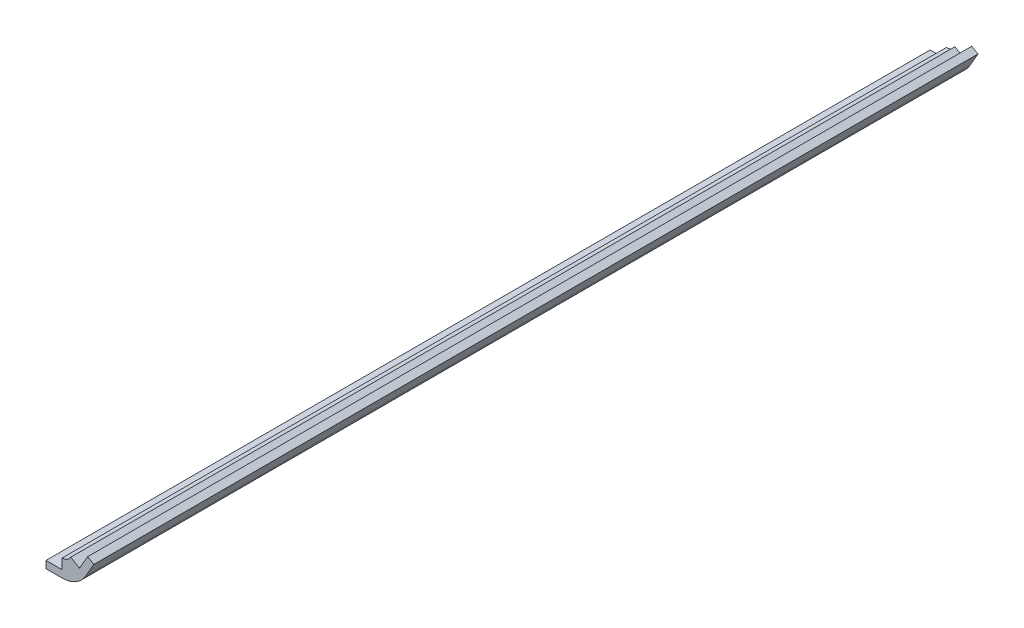
SolidWorks part; units mm, degrees
ref_plane "Front Plane" through (0, 0, 0) normal (0, 0, 1) x (1, 0, 0)
ref_plane "Top Plane" through (0, 0, 0) normal (0, 1, 0) x (1, 0, 0)
ref_plane "Right Plane" through (0, 0, 0) normal (1, 0, 0) x (0, 0, -1)
ref_axis "Axis1" through (0, 0, -88.99) along (0, 0, 1)
sketch "Sketch16" plane through (0, 0, 0) normal (0, 1, 0) x (1, 0, 0)
  line L0 (0, -127) -> (0, 127) construction
  point P2 (0, 0)
  dimension "D1" = 254
sketch "Sketch2" plane through (0, 0, 0) normal (0, 0, 1) x (1, 0, 0)
  line L0 (-7.3025, -1.5) -> (-2.54, -1.5) construction
  line L1 (-7.3025, -1.5) -> (-7.3025, 1.5) construction
  line L2 (-2.54, -1.5) -> (-2.54, 1.5) construction
  line L3 (-7.3025, 1.5) -> (-2.54, 1.5) construction
  line L4 (-2.54, 0) -> (0, 0) construction
  line L5 (0, 0) -> (1.27, 2.1997) construction
  line L6 (2.569, 1.4497) -> (-0.029, 2.9497) construction
  line L7 (2.569, 1.4497) -> (4.9503, 5.5742) construction
  line L8 (-0.029, 2.9497) -> (2.3522, 7.0742) construction
  line L9 (4.9503, 5.5742) -> (2.3522, 7.0742) construction
  point P7 (1.27, 2.1997)
  point P16 (-0.866, 1.5)
  dimension "D1" = 3
  dimension "D2" = 4.7625
  dimension "D3" = 2.54
  dimension "D4" = 120
ref_plane "Plane1" through (0, 0, 0) normal (-0.866, 0.5, 0) x (0.5, 0.866, 0)
sketch "Sketch7" plane through (0, 0, 0) normal (0, 0, 1) x (1, 0, 0)
  line L0 (-7.3025, -1.5) -> (-2.54, -1.5)
  line L1 (-7.3025, -1.5) -> (-7.3025, -3.6212)
  line L2 (-2.54, -1.5) -> (-2.54, -3.6212)
  line L3 (-7.3025, -3.6212) -> (-2.54, -3.6212)
  dimension "D1" = 2.1212
extrude "Boss-Extrude2" add sketch "Sketch7" along normal mid plane 260.35 separate body
sketch "Sketch8" plane through (0, 0, 0) normal (0, 0, 1) x (1, 0, 0)
  line L0 (2.569, 1.4497) -> (4.9503, 5.5742)
  line L1 (2.569, 1.4497) -> (4.4061, 0.3891)
  line L2 (4.9503, 5.5742) -> (6.7873, 4.5135)
  line L3 (4.4061, 0.3891) -> (6.7873, 4.5135)
  line L4 (-2.54, -3.6212) -> (-2.54, -1.5) construction
extrude "Boss-Extrude3" add sketch "Sketch8" along normal mid plane 260.35
sketch "Sketch11" plane through (0, 0, 0) normal (0, 0, 1) x (1, 0, 0)
  line L1 (-2.54, -1.5) -> (-7.3025, -1.5)
  line L2 (-7.3025, -1.5) -> (-7.3025, -3.6212)
  line L8 (6.7873, 4.5135) -> (4.9503, 5.5742)
  line L9 (4.9503, 5.5742) -> (2.569, 1.4497)
  line L13 (2.569, 1.4497) -> (-0.029, 2.9497)
  line L14 (-0.029, 2.9497) -> (-0.866, 1.5) construction
  line L15 (-0.866, 1.5) -> (-2.54, 1.5) construction
  line L17 (-2.54, 1.5) -> (-2.54, -1.5)
  line L18 (6.7873, 4.5135) -> (4.4061, 0.3891)
  line L19 (2.569, 1.4497) -> (4.4061, 0.3891) construction
  line L20 (-2.54, -3.6212) -> (-7.3025, -3.6212)
  arc A0 (-0.029, 2.9497) -> (-2.54, 1.5) centre (-2.54, 4.3994) cw
  arc A1 (4.4061, 0.3891) -> (-2.54, -3.6212) centre (-2.54, 4.3994) cw
extrude "Boss-Extrude4" add sketch "Sketch11" along normal mid plane 260.35
ref_plane "Midplane" through (0, 0, 0) normal (0.866, 0.5, 0) x (0.5, -0.866, 0)
equation "\"plate_thickness\"= 3mm"
equation "\"D1@Sketch2\"=\"plate_thickness\""
equation "\"joiner_lip_width\"= .1875"
equation "\"D2@Sketch2\"=\"joiner_lip_width\""
equation "\"face_gap\"=0.1"
equation "\"D3@Sketch2\"=\"face_gap\""
equation "\"inside_angle\"= 180 - arccos ( 1 / 2 )"
equation "\"joiner_thickness\"= 0.0835128"
equation "\"edge_length\"= 10"
equation "\"Face1_TopLip\"= \"angle\" * 2"
equation "\"Face1_BottomLip\"= \"angle\" * 2"
equation "\"Face2_TopLip\"= 45deg"
equation "\"Face2_BottomLip\"= 45deg"
equation "\"D1@Sketch7\"=\"joiner_thickness\""
equation "\"D1@Boss-Extrude2\"=\"Extrude_to\""
equation "\"D1@Boss-Extrude3\"=\"Extrude_to\""
equation "\"D1@Boss-Extrude4\"=\"Extrude_to\""
equation "\"Extrude_to\"= \"edge_length\" + .25"
equation "\"D1@Sketch16\"=\"edge_length\""
equation "\"angle\"= atn ( 0.1 / ( ( 3.7085 - 3.0793 ) / 2 ) )"
equation "\"D4@Sketch2\"=\"inside_angle\""
equation "\"D2@Sketch5\"=\"Face2_TopLip\"/2"
equation "\"D1@Sketch5\"=\"Face2_BottomLip\"/2"
equation "\"D2@Sketch4\"=\"Face1_TopLip\"/2"
equation "\"D1@Sketch4\"=\"Face1_BottomLip\"/2"
equation "\"D1\" = \"edge_length\""
equation "\"D2@Sketch12\"=\"Face1_TopLip\"/2"
equation "\"D1@Sketch12\"=\"Face1_BottomLip\"/2"
